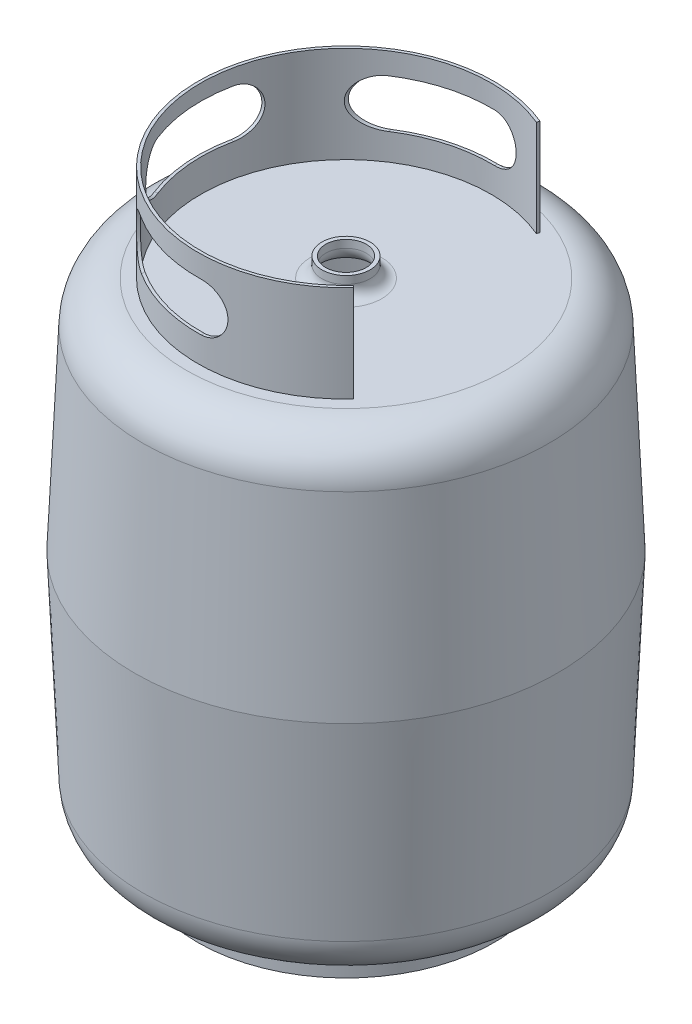
SolidWorks part; units mm, degrees
material "Alliage 1060"
ref_plane "Plan de face" through (0, 0, 0) normal (0, 0, 1) x (1, 0, 0)
ref_plane "Plan de dessus" through (0, 0, 0) normal (0, 1, 0) x (1, 0, 0)
ref_plane "Plan de droite" through (0, 0, 0) normal (1, 0, 0) x (0, 0, -1)
sketch "Esquisse1" plane through (0, 0, 0) normal (0, 0, 1) x (1, 0, 0)
  line L0 (1.1309, 254.0674) -> (1.1309, 234.0674)
  line L1 (1.1309, 234.0674) -> (-182.6191, 234.0674)
  line L2 (-182.6191, 234.0674) -> (-193.316, -10.9326)
  line L3 (-182.6191, -255.9326) -> (26.1309, -255.9326)
  line L4 (-193.316, -10.9326) -> (-182.6191, -255.9326)
  line L5 (26.1309, -255.9326) -> (26.1309, 351.9756) construction
  line L6 (1.1309, 254.0674) -> (26.1309, 254.0674)
  line L7 (26.1309, 254.0674) -> (26.1309, -255.9326)
  point P2 (1.1309, 244.0674)
  dimension "D1" = 92.5
  dimension "D2" = 92.5
  dimension "D3" = 20
  dimension "D4" = 208.75
  dimension "D5" = 490
  dimension "D6" = 245
  dimension "D7" = 25
revolve "Révolution2" add sketch "Esquisse1" angle 360 about L5
fillet "Congé1" radius 12 1 edges at (26.1309, 234.0674, -25)
fillet "Congé2" radius 45 1 edges at (26.1309, 234.0674, -208.75)
fillet "Congé3" radius 45 1 edges at (26.1309, -255.9326, -208.75)
shell "Coque12" thickness 4 removed face at (26.1309, 254.0674, -25)
sketch "Esquisse2" plane through (0, 234.0674, 0) normal (0, 1, 0) x (1, 0, 0)
  line L0 (84.7247, 138.812) -> (85.8913, 141.5759)
  line L1 (136.5314, -102.5366) -> (138.7295, -104.5782)
  arc A0 (85.8913, 141.5759) -> (138.7295, -104.5782) centre (26.1309, 0) ccw
  circle A1 centre (26.1309, 0) radius 165.6719 construction
  arc A2 (84.7247, 138.812) -> (136.5314, -102.5366) centre (26.1309, 0) ccw
  dimension "D1" = 12
  dimension "D2" = 3
extrude "Boss.-Extru.1" add sketch "Esquisse2" along normal blind 100
sketch "Esquisse5" plane through (0, 0, 0) normal (1, 0, 0) x (0, 0, -1)
  line L0 (-55.1165, 292.64) -> (30.8835, 292.64) construction
  line L1 (-55.1165, 317.64) -> (30.8835, 317.64)
  line L2 (-55.1165, 267.64) -> (30.8835, 267.64)
  arc A0 (-55.1165, 317.64) -> (-55.1165, 267.64) centre (-55.1165, 292.64) ccw
  arc A1 (30.8835, 267.64) -> (30.8835, 317.64) centre (30.8835, 292.64) ccw
  point P2 (-12.1165, 292.64)
  dimension "D2" = 25
  dimension "D1" = 86
extrude "Enlèv. mat.-Extru.1" cut sketch "Esquisse5" against normal through all both and the other way through all
sketch "Esquisse6" plane through (0, 0, 0) normal (0, 0, 1) x (1, 0, 0)
  line L0 (-56.3176, 286.6182) -> (29.6824, 286.6182) construction
  line L1 (-56.3176, 311.6182) -> (29.6824, 311.6182)
  line L2 (-56.3176, 261.6182) -> (29.6824, 261.6182)
  arc A0 (-56.3176, 311.6182) -> (-56.3176, 261.6182) centre (-56.3176, 286.6182) ccw
  arc A1 (29.6824, 261.6182) -> (29.6824, 311.6182) centre (29.6824, 286.6182) ccw
  point P2 (-13.3176, 286.6182)
extrude "Enlèv. mat.-Extru.2" cut sketch "Esquisse6" against normal through all both and the other way through all
sketch "Esquisse7" plane through (0, -255.9326, 0) normal (0, -1, 0) x (1, 0, 0)
  circle A0 centre (26.1309, 0) radius 153.6719
  circle A1 centre (26.1309, 0) radius 165.6719 construction
  circle A2 centre (26.1309, 0) radius 150.6719
  dimension "D1" = 12
  dimension "D2" = 3
extrude "Boss.-Extru.2" add sketch "Esquisse7" along normal blind 30
equation "\"A\"= 417.5"
equation "\"B\"= 490"
equation "\"D4@Esquisse1\"=\"A\"/2"
equation "\"D5@Esquisse1\"=\"B\""
equation "\"D6@Esquisse1\"=\"B\"/2"
